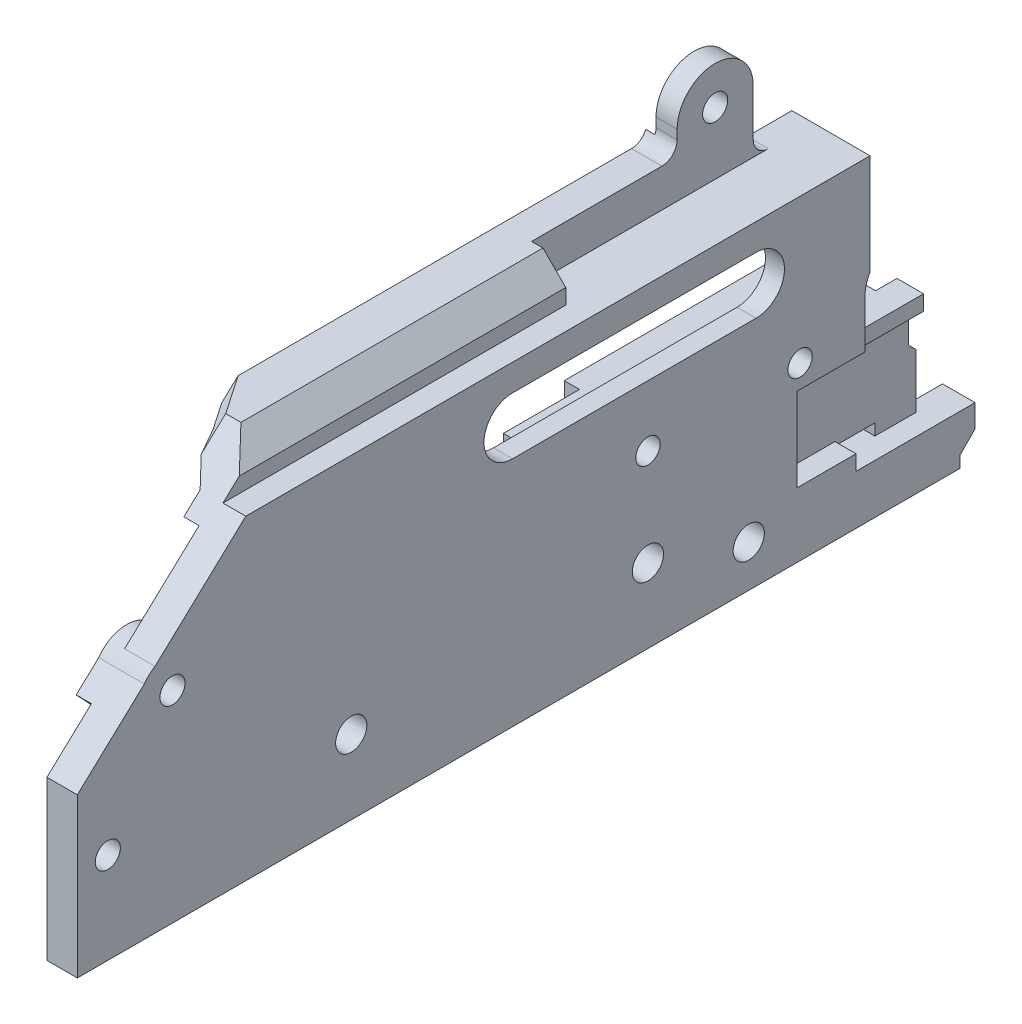
SolidWorks part; units mm, degrees
ref_plane "前视基准面" through (0, 0, 0) normal (0, 0, 1) x (1, 0, 0)
ref_plane "上视基准面" through (0, 0, 0) normal (0, 1, 0) x (1, 0, 0)
ref_plane "右视基准面" through (0, 0, 0) normal (1, 0, 0) x (0, 0, -1)
other "Configuration Table"
sketch "草图1" plane through (0, 0, 0) normal (1, 0, 0) x (0, 0, -1)
  line L0 (0, 0) -> (20, 0) construction
  line L2 (29.2, 6.5) -> (-4, 6.5)
  line L3 (29.2, 6.5) -> (29.2, -15.5)
  line L4 (29.2, -15.5) -> (-4, -15.5)
  line L5 (-4, 6.5) -> (-4, -15.5)
  circle A0 centre (0, 0) radius 1.6
  circle A1 centre (20, 0) radius 1.6
  dimension "D1" = 20
  dimension "D2" = 3.2
  dimension "D4" = 9.2
  dimension "D6" = 4
  dimension "D3" = 6.5
  dimension "D5" = 22
extrude "凸台-拉伸1" add sketch "草图1" along normal blind 7
sketch "草图2" plane through (7, 0, 0) normal (1, 0, 0) x (0, 0, -1)
  line L1 (-4, 6.5) -> (29.2, 6.5)
  line L2 (-4, 6.5) -> (-4, 17)
  line L3 (-4, 17) -> (29.2, 17)
  line L4 (29.2, 6.5) -> (29.2, 17)
  dimension "D1" = 10.5
extrude "凸台-拉伸2" add sketch "草图2" against normal offset from surface (2 mm away) 5 up to face at (0, 0, -1.6)
sketch "草图3" plane through (0, 0, 4) normal (0, 0, 1) x (1, 0, 0)
  line L1 (7, -15.5) -> (1, -15.5)
  line L2 (7, -15.5) -> (7, 6.5)
  line L3 (7, 6.5) -> (3, 6.5)
  line L4 (1, -15.5) -> (1, 4.5)
  line L5 (3, 6.5) -> (3, 4.5)
  line L6 (3, 4.5) -> (1, 4.5)
  line L7 (5, 6.5) -> (0, 6.5) construction
  dimension "D1" = 6
  dimension "D2" = 2
  dimension "D3" = 2
extrude "凸台-拉伸3" add sketch "草图3" along normal blind 60
sketch "草图4" plane through (0, 0, 4) normal (0, 0, 1) x (1, 0, 0)
  line L4 (5, 6.5) -> (7, 6.5)
  line L5 (7, 6.5) -> (7, 17)
  line L6 (7, 17) -> (5, 17)
  line L7 (5, 17) -> (5, 6.5)
  line L8 (5, 6.5) -> (7, 6.5)
  line L9 (7, 6.5) -> (7, 17)
  line L10 (7, 17) -> (5, 17)
  line L11 (5, 17) -> (5, 6.5)
  dimension "D1" = 0
extrude "凸台-拉伸4" add sketch "草图4" along normal blind 38.5
sketch "草图5" plane through (0, 0, 42.5) normal (0, 0, 1) x (1, 0, 0)
  line L0 (7, 6.5) -> (7, 17) construction
  line L1 (7, 6.5) -> (3, 6.5)
  line L2 (7, 6.5) -> (7, 17)
  line L3 (7, 17) -> (3, 17)
  line L4 (3, 6.5) -> (3, 17)
  line L5 (7, 17) -> (5, 17) construction
extrude "凸台-拉伸5" add sketch "草图5" along normal blind 2
sketch "草图6" plane through (0, 0, 44.5) normal (0, 0, 1) x (1, 0, 0)
  line L4 (7, 6.5) -> (7, 17)
  line L5 (7, 17) -> (3, 17)
  line L6 (3, 17) -> (3, 6.5)
  line L7 (3, 6.5) -> (7, 6.5)
  line L8 (7, 6.5) -> (7, 17)
  line L9 (7, 17) -> (3, 17)
  line L10 (3, 17) -> (3, 6.5)
  line L11 (3, 6.5) -> (7, 6.5)
  dimension "D1" = 0
extrude "凸台-拉伸6" add sketch "草图6" along normal up to surface (19.5 mm away) up to face at (3.6667, -1.5, 64)
sketch "草图7" plane through (0, 17, 0) normal (0, 1, 0) x (1, 0, 0)
  line L0 (1, -64) -> (1, -4) construction
  line L1 (7, 29.2) -> (1, 29.2)
  line L2 (7, 29.2) -> (7, -64)
  line L3 (7, -64) -> (1, -64)
  line L4 (1, 29.2) -> (1, -64)
  line L5 (7, -64) -> (3, -64) construction
extrude "凸台-拉伸7" add sketch "草图7" along normal blind 2
sketch "草图8" plane through (1, 0, 0) normal (-1, 0, 0) x (0, 0, 1)
  line L1 (-29.2, 19) -> (64, 19)
  line L2 (-29.2, 19) -> (-29.2, 24)
  line L3 (-29.2, 24) -> (64, 24)
  line L4 (64, 19) -> (64, 24)
  dimension "D1" = 5
extrude "凸台-拉伸8" add sketch "草图8" against normal blind 3
sketch "草图10" plane through (1, 0, 0) normal (-1, 0, 0) x (0, 0, 1)
  line L1 (-29.2, 24) -> (64, 24)
  line L2 (-29.2, 24) -> (-29.2, 22)
  line L3 (-29.2, 22) -> (64, 22)
  line L4 (64, 24) -> (64, 22)
  line L5 (64, 24) -> (64, 17) construction
  dimension "D1" = 2
extrude "凸台-拉伸9" add sketch "草图10" along normal blind 5.5
sketch "草图12" plane through (-4.5, 0, 0) normal (-1, 0, 0) x (0, 0, 1)
  line L0 (64, 24) -> (-29.2, 24) construction
  line L1 (-29.2, 22) -> (-11.2, 22)
  line L2 (-29.2, 22) -> (-29.2, 24)
  line L3 (-29.2, 24) -> (-11.2, 24)
  line L4 (-11.2, 22) -> (-11.2, 24)
  dimension "D1" = 18
extrude "切除-拉伸1" cut sketch "草图12" against normal up to surface (5.5 mm away) up to face at (1, 19.5, 17.4)
sketch "草图13" plane through (1, 0, 0) normal (-1, 0, 0) x (0, 0, 1)
  line L0 (-11.2, 22) -> (64, 22) construction
  line L1 (10.8, 22) -> (-29.2, 22)
  line L2 (10.8, 22) -> (10.8, 17)
  line L3 (10.8, 17) -> (-29.2, 17)
  line L4 (-29.2, 22) -> (-29.2, 17)
  dimension "D1" = 40
extrude "凸台-拉伸10" add sketch "草图13" along normal blind 3.5
sketch "草图14" plane through (-2.5, 0, 0) normal (-1, 0, 0) x (0, 0, 1)
  line L0 (-29.2, 17) -> (10.8, 17) construction
  line L1 (-11.2, 19.8) -> (-9.2, 19.8)
  line L2 (-11.2, 19.8) -> (-11.2, 17)
  line L3 (-11.2, 17) -> (-9.2, 17)
  line L4 (-9.2, 19.8) -> (-9.2, 17)
  line L5 (10.8, 22) -> (-11.2, 22) construction
  line L6 (-11.2, 22) -> (-11.2, 24) construction
  dimension "D1" = 2
  dimension "D2" = 2.2
sketch "草图15" plane through (4, 0, 0) normal (1, 0, 0) x (0, 0, -1)
  line L0 (29.2, 19) -> (-64, 19) construction
  line L1 (29.2, 24) -> (13.7, 24)
  line L2 (29.2, 24) -> (29.2, 19)
  line L3 (29.2, 19) -> (13.7, 19)
  line L4 (13.7, 24) -> (13.7, 19)
  line L6 (11.2, 22) -> (11.2, 24) construction
  dimension "D1" = 2.5
extrude "切除-拉伸2" cut sketch "草图15" against normal up to next
sketch "草图16" plane through (0, 22, 0) normal (0, 1, 0) x (1, 0, 0)
  line L4 (1, 11.2) -> (1, 13.7)
  line L5 (1, 13.7) -> (-2.5, 13.7)
  line L6 (-2.5, 13.7) -> (-2.5, 11.2)
  line L7 (-2.5, 11.2) -> (1, 11.2)
  line L8 (1, 11.2) -> (1, 13.7)
  line L9 (1, 13.7) -> (-2.5, 13.7)
  line L10 (-2.5, 13.7) -> (-2.5, 11.2)
  line L11 (-2.5, 11.2) -> (1, 11.2)
  dimension "D1" = 0
extrude "凸台-拉伸12" add sketch "草图16" along normal up to surface (2 mm away) up to face at (0.1667, 24, 13.0333)
sketch "草图17" plane through (7, 0, 0) normal (1, 0, 0) x (0, 0, -1)
  line L0 (-47.5, 24) -> (-64, 8.6135)
  line L1 (-64, 24) -> (13.7, 24) construction
  line L2 (-64, -15.5) -> (-64, 19) construction
  line L3 (-64, 8.6135) -> (-64, 24)
  line L4 (-64, 24) -> (-47.5, 24)
  dimension "D1" = 133
  dimension "D2" = 16.5
extrude "切除-拉伸3" cut sketch "草图17" against normal up to next
chamfer "倒角1" distance 3.5 angle 45 1 edges at (-4.5, 23, 48.5724)
sketch "草图18" plane through (-2.5, 0, 0) normal (-1, 0, 0) x (0, 0, 1)
  line L0 (-13.7, 19) -> (-13.7, 24) construction
  line L1 (-29.2, 19) -> (-13.7, 19) construction
  line L2 (-11.337, 27.2) -> (-11.337, 24)
  line L3 (-13.7, 24) -> (-11.2, 24) construction
  line L4 (-11.337, 24) -> (-13.7, 24)
  line L5 (-13.7, 24) -> (-13.7, 19)
  line L6 (-13.7, 19) -> (-21.337, 19)
  line L7 (-21.337, 19) -> (-21.337, 27.2)
  circle A0 centre (-16.337, 27.2) radius 1.65
  arc A1 (-11.337, 27.2) -> (-21.337, 27.2) centre (-16.337, 27.2) ccw
  dimension "D1" = 2.637
  dimension "D2" = 8.2
  dimension "D3" = 3.3
  dimension "D4" = 10
extrude "凸台-拉伸13" add sketch "草图18" against normal blind 2
fillet "圆角1" radius 2 2 edges at (-1.5, 24, -11.337) (-1.5, 19, -21.337)
sketch "草图19" plane through (0, 24, 0) normal (0, 1, 0) x (1, 0, 0)
  line L0 (-0.5, 9.337) -> (-0.5, 11.337) construction
  line L1 (4, 13.7) -> (-0.5, 13.7)
  line L2 (4, 13.7) -> (4, -7.8)
  line L3 (4, -7.8) -> (-0.5, -7.8)
  line L4 (-0.5, 13.7) -> (-0.5, -7.8)
  line L5 (-2.5, -10.8) -> (1, -10.8) construction
  dimension "D1" = 3
extrude "切除-拉伸4" cut sketch "草图19" against normal up to surface (5 mm away) up to face at (2, 19, -3.3438)
chamfer "倒角2" distance 3 angle 45 2 edges at (4, 24, 27.65) (1, 22, 30.2224)
sketch "草图20" plane through (7, 0, 0) normal (1, 0, 0) x (0, 0, -1)
  line L0 (-64, -15.5) -> (-64, 8.6135) construction
  line L1 (-64, -15.5) -> (29.2, -15.5) construction
  circle A0 centre (-62.5, 4) radius 1.65
  dimension "D1" = 1.5
  dimension "D2" = 19.5
  dimension "D3" = 3.3
extrude "切除-拉伸5" cut sketch "草图20" against normal up to next
sketch "草图21" plane through (1, 0, 0) normal (-1, 0, 0) x (0, 0, 1)
  circle A0 centre (62.5, 4) radius 1.65
  circle A1 centre (62.5, 4) radius 4.5
  dimension "D1" = 9
extrude "凸台-拉伸14" add sketch "草图21" against normal up to surface (6 mm away) up to face at (7, 3.3734, 35.3303)
sketch "草图22" plane through (1, 0, 0) normal (-1, 0, 0) x (0, 0, 1)
  line L3 (66.1986, 6.5633) -> (75, -1.6442)
  line L4 (75, -1.6442) -> (75, -15.5)
  line L5 (75, -15.5) -> (64, -15.5)
  line L6 (55.0066, 17) -> (64, 8.6135) construction
  line L7 (64, -0.2426) -> (64, -15.5)
  circle A2 centre (62.5, 4) radius 1.65 construction
  arc A3 (64, -0.2426) -> (58.0279, 4.5) centre (62.5, 4) ccw construction
  arc A4 (64, -0.2426) -> (66.1986, 6.5633) centre (62.5, 4) ccw
  dimension "D1" = 12.5
extrude "凸台-拉伸15" add sketch "草图22" against normal up to surface (6 mm away) up to face at (7, 3.3734, 36.2088)
sketch "草图23" plane through (7, 0, 0) normal (1, 0, 0) x (0, 0, -1)
  line L0 (-64, 8.6135) -> (-64.799, 7.8684)
  line L1 (-64.799, 7.8684) -> (-64, 8.2426)
  line L2 (-64, 8.2426) -> (-64, 8.6135)
  line L3 (-64, 8.6135) -> (-52.8618, 19) construction
  arc A0 (-64, 8.2426) -> (-66.1986, 6.5633) centre (-62.5, 4) ccw construction
extrude "凸台-拉伸16" add sketch "草图23" against normal up to surface (4 mm away) up to face at (3, 9.2872, 41.6414)
sketch "草图24" plane through (1, 0, 0) normal (-1, 0, 0) x (0, 0, 1)
  line L0 (75, -15.5) -> (75, -1.6442) construction
  line L1 (75, -15.5) -> (4, -15.5) construction
  circle A0 centre (71, -10.5) radius 1.65
  dimension "D1" = 3.3
  dimension "D2" = 4
  dimension "D3" = 5
extrude "切除-拉伸6" cut sketch "草图24" against normal up to next
sketch "草图25" plane through (5, 0, 0) normal (-1, 0, 0) x (0, 0, 1)
  line L0 (-29.2, 11.75) -> (42.5, 11.75) construction
  line L1 (-29.2, 6.5) -> (-29.2, 17) construction
  line L2 (42.5, 17) -> (42.5, 6.5) construction
  line L3 (17.8, 11.75) -> (-14.2, 11.75) construction
  line L4 (17.8, 8) -> (-14.2, 8)
  line L5 (17.8, 15.5) -> (-14.2, 15.5)
  arc A0 (17.8, 8) -> (17.8, 15.5) centre (17.8, 11.75) ccw
  arc A1 (-14.2, 15.5) -> (-14.2, 8) centre (-14.2, 11.75) ccw
  point P8 (1.8, 11.75)
  dimension "D1" = 47
  dimension "D2" = 15
  dimension "D3" = 7.5
extrude "切除-拉伸7" cut sketch "草图25" against normal up to next
sketch "草图26" plane through (0, 0, 42.5) normal (0, 0, -1) x (-1, 0, 0)
  line L4 (-5, 17) -> (-5, 6.5)
  line L5 (-5, 6.5) -> (-3, 6.5)
  line L6 (-3, 6.5) -> (-3, 17)
  line L7 (-3, 17) -> (-5, 17)
  line L8 (-5, 17) -> (-5, 6.5)
  line L9 (-5, 6.5) -> (-3, 6.5)
  line L10 (-3, 6.5) -> (-3, 17)
  line L11 (-3, 17) -> (-5, 17)
  dimension "D1" = 0
extrude "切除-拉伸8" cut sketch "草图26" against normal blind 5
sketch "草图27" plane through (0, 0, 4) normal (0, 0, 1) x (1, 0, 0)
  line L1 (1, 4.5) -> (3, 4.5)
  line L2 (1, 4.5) -> (1, 6.5)
  line L3 (1, 6.5) -> (3, 6.5)
  line L4 (3, 4.5) -> (3, 6.5)
extrude "凸台-拉伸17" add sketch "草图27" along normal blind 10
sketch "草图28" plane through (1, 0, 0) normal (-1, 0, 0) x (0, 0, 1)
  line L0 (67, 1.4943) -> (67, -15.5)
  line L2 (75, -15.5) -> (4, -15.5) construction
  line L3 (67, -15.5) -> (75, -15.5)
  line L4 (75, -15.5) -> (75, -1.6442)
  line L5 (75, -1.6442) -> (69.1556, 3.8058)
  line L6 (69.1556, 3.8058) -> (67, 1.4943)
  line L7 (75, -1.6442) -> (66.1986, 6.5633) construction
  circle A0 centre (62.5, 4) radius 1.65 construction
  dimension "D3" = 5
  dimension "D1" = 8
  dimension "D2" = 137
extrude "切除-拉伸9" cut sketch "草图28" against normal blind 2
sketch "草图29" plane through (7, 0, 0) normal (1, 0, 0) x (0, 0, -1)
  circle A0 centre (34, 3.1) radius 5.5
  circle A1 centre (20, 0) radius 1.6 construction
  dimension "D1" = 3.1
  dimension "D2" = 14
  dimension "D3" = 11
extrude "切除-拉伸10" cut sketch "草图29" against normal up to next
sketch "草图30" plane through (1, 0, 0) normal (-1, 0, 0) x (0, 0, 1)
  line L0 (4, 6.5) -> (4, -15.5) construction
  line L1 (4, -4.5) -> (67, -4.5)
  line L2 (4, -4.5) -> (4, -6.5)
  line L3 (4, -6.5) -> (67, -6.5)
  line L4 (67, -4.5) -> (67, -6.5)
  line L5 (67, 1.4943) -> (67, -15.5) construction
  circle A0 centre (0, 0) radius 1.6 construction
  dimension "D1" = 4.5
  dimension "D2" = 2
extrude "凸台-拉伸18" add sketch "草图30" along normal up to surface (1 mm away) up to face at (0, -1.9667, -18.0167)
sketch "草图31" plane through (5, 0, 0) normal (-1, 0, 0) x (0, 0, 1)
  line L0 (-14.2, 8) -> (17.8, 8) construction
  line L1 (17.8, 15.5) -> (-14.2, 15.5) construction
  line L2 (-14.2, 8) -> (17.8, 8)
  line L3 (17.8, 15.5) -> (-14.2, 15.5)
  line L4 (-29.2, 6.5) -> (47.5, 6.5)
  line L5 (47.5, 6.5) -> (47.5, 17)
  line L6 (47.5, 17) -> (-29.2, 17)
  line L7 (-29.2, 17) -> (-29.2, 6.5)
  line L8 (-29.2, 6.5) -> (47.5, 6.5)
  line L9 (47.5, 6.5) -> (47.5, 17)
  line L10 (47.5, 17) -> (-29.2, 17)
  line L11 (-29.2, 17) -> (-29.2, 6.5)
  arc A0 (17.8, 8) -> (17.8, 15.5) centre (17.8, 11.75) ccw construction
  arc A1 (-14.2, 15.5) -> (-14.2, 8) centre (-14.2, 11.75) ccw construction
  arc A2 (17.8, 8) -> (17.8, 15.5) centre (17.8, 11.75) ccw
  arc A3 (-14.2, 15.5) -> (-14.2, 8) centre (-14.2, 11.75) ccw
  dimension "D1" = 0
sketch "草图32" plane through (-2.5, 0, 0) normal (-1, 0, 0) x (0, 0, 1)
  line L8 (-11.2, 22) -> (-11.2, 25.2725)
  line L9 (-11.337, 26) -> (-11.337, 27.2)
  line L10 (-21.337, 27.2) -> (-21.337, 21)
  line L11 (-23.337, 19) -> (-29.2, 19)
  line L12 (-29.2, 19) -> (-29.2, 17)
  line L13 (-29.2, 17) -> (10.8, 17)
  line L14 (10.8, 17) -> (10.8, 22)
  line L15 (10.8, 22) -> (-11.2, 22)
  line L16 (-11.2, 22) -> (-11.2, 25.2725)
  line L17 (-11.337, 26) -> (-11.337, 27.2)
  line L18 (-21.337, 27.2) -> (-21.337, 21)
  line L19 (-23.337, 19) -> (-29.2, 19)
  line L20 (-29.2, 19) -> (-29.2, 17)
  line L21 (-29.2, 17) -> (10.8, 17)
  line L22 (10.8, 17) -> (10.8, 22)
  line L23 (10.8, 22) -> (-11.2, 22)
  circle A0 centre (-16.337, 27.2) radius 1.65 construction
  circle A1 centre (-16.337, 27.2) radius 1.65
  arc A3 (-11.337, 26) -> (-11.2, 25.2725) centre (-9.337, 26) ccw
  arc A4 (-11.337, 27.2) -> (-21.337, 27.2) centre (-16.337, 27.2) ccw
  arc A5 (-23.337, 19) -> (-21.337, 21) centre (-23.337, 21) ccw
  arc A6 (-11.337, 26) -> (-11.2, 25.2725) centre (-9.337, 26) ccw
  arc A7 (-11.337, 27.2) -> (-21.337, 27.2) centre (-16.337, 27.2) ccw
  arc A8 (-23.337, 19) -> (-21.337, 21) centre (-23.337, 21) ccw
  dimension "D1" = 0
extrude "凸台-拉伸19" add sketch "草图32" along normal blind 0.775
sketch "草图34" plane through (0, -15.5, 0) normal (0, -1, 0) x (1, 0, 0)
  line L8 (3, 75) -> (3, 67)
  line L9 (3, 67) -> (1, 67)
  line L10 (1, 67) -> (1, 4)
  line L11 (1, 4) -> (0, 4)
  line L12 (0, 4) -> (0, -29.2)
  line L13 (0, -29.2) -> (7, -29.2)
  line L14 (7, -29.2) -> (7, 75)
  line L15 (7, 75) -> (3, 75)
  line L16 (3, 75) -> (3, 67)
  line L17 (3, 67) -> (1, 67)
  line L18 (1, 67) -> (1, 4)
  line L19 (1, 4) -> (0, 4)
  line L20 (0, 4) -> (0, -29.2)
  line L21 (0, -29.2) -> (7, -29.2)
  line L22 (7, -29.2) -> (7, 75)
  line L23 (7, 75) -> (3, 75)
  dimension "D1" = 0
extrude "凸台-拉伸20" add sketch "草图34" along normal blind 5.5
sketch "草图35" plane through (0, 0, 0) normal (-1, 0, 0) x (0, 0, 1)
  line L1 (-24.2, -11) -> (-29.2, -11)
  line L2 (-24.2, -11) -> (-24.2, -21)
  line L3 (-24.2, -21) -> (-29.2, -21)
  line L4 (-29.2, -11) -> (-29.2, -21)
  dimension "D1" = 5
  dimension "D2" = 10
extrude "切除-拉伸12" cut sketch "草图35" against normal blind 1.225
sketch "草图36" plane through (0, 0, -29.2) normal (0, 0, -1) x (-1, 0, 0)
  line L1 (-1.225, -21) -> (-5.225, -21)
  line L2 (-1.225, -21) -> (-1.225, -11)
  line L3 (-1.225, -11) -> (-5.225, -11)
  line L4 (-5.225, -21) -> (-5.225, -11)
  dimension "D1" = 10
  dimension "D2" = 4
extrude "凸台-拉伸21" add sketch "草图36" along normal blind 5
sketch "草图37" plane through (5.225, 0, 0) normal (1, 0, 0) x (0, 0, -1)
  line L0 (34.2, -11) -> (34.2, -21) construction
  line L1 (33.6, -16) -> (28.85, -16)
  line L2 (33.6, -16) -> (33.6, -13)
  line L3 (33.6, -13) -> (28.85, -13)
  line L4 (28.85, -16) -> (28.85, -13)
  line L5 (34.2, -21) -> (29.2, -21) construction
  dimension "D1" = 5
  dimension "D2" = 3
  dimension "D3" = 5.35
  dimension "D4" = 0.6
extrude "切除-拉伸13" cut sketch "草图37" against normal up to next and the other way up to next
sketch "草图38" plane through (5.225, 0, 0) normal (1, 0, 0) x (0, 0, -1)
  line L0 (34.2, -11) -> (34.2, -21) construction
  line L1 (34.2, -14) -> (19.6, -14)
  line L2 (34.2, -14) -> (34.2, -3)
  line L3 (34.2, -3) -> (19.6, -3)
  line L4 (19.6, -14) -> (19.6, -3)
  line L5 (33.6, -16) -> (29.2, -16) construction
  line L7 (28.85, -16) -> (28.85, -13) construction
  dimension "D1" = 2
  dimension "D2" = 9.25
  dimension "D3" = 11
extrude "切除-拉伸14" cut sketch "草图38" along normal up to next and the other way blind 1
sketch "草图39" plane through (0, 0, -34.2) normal (0, 0, -1) x (-1, 0, 0)
  line L1 (-2.725, -1) -> (-4.225, -1)
  line L2 (-2.725, -1) -> (-2.725, -21)
  line L3 (-2.725, -21) -> (-4.225, -21)
  line L4 (-4.225, -1) -> (-4.225, -21)
  line L5 (-5.225, -21) -> (-1.225, -21) construction
  line L6 (-5.225, -14) -> (-5.225, -21) construction
  line L7 (-1.225, -11) -> (0, -11) construction
  dimension "D1" = 2.5
  dimension "D2" = 1
  dimension "D3" = 10
extrude "凸台-拉伸22" add sketch "草图39" along normal blind 5.8 and the other way up to next
sketch "草图40" plane through (0, 0, -29.2) normal (0, 0, -1) x (-1, 0, 0)
  line L1 (-1.225, -11) -> (-2.725, -11)
  line L2 (-1.225, -11) -> (-1.225, -1)
  line L3 (-1.225, -1) -> (-2.725, -1)
  line L4 (-2.725, -11) -> (-2.725, -1)
extrude "凸台-拉伸23" add sketch "草图40" along normal up to surface (5 mm away) up to face at (1.975, -16, -34.2)
sketch "草图41" plane through (4.225, 0, 0) normal (1, 0, 0) x (0, 0, -1)
  line L1 (40, -1) -> (39, -1)
  line L2 (40, -1) -> (40, -8)
  line L3 (40, -8) -> (39, -8)
  line L4 (39, -1) -> (39, -8)
  dimension "D1" = 1
  dimension "D2" = 7
extrude "切除-拉伸15" cut sketch "草图41" against normal up to next
chamfer "倒角3" distance 1 angle 45 1 edges at (3.475, -8, -39)
sketch "草图42" plane through (0, 0, -29.2) normal (0, 0, -1) x (-1, 0, 0)
  line L1 (-4.225, -21) -> (-7, -21)
  line L2 (-4.225, -21) -> (-4.225, -16)
  line L3 (-4.225, -16) -> (-7, -16)
  line L4 (-7, -21) -> (-7, -16)
extrude "凸台-拉伸24" add sketch "草图42" along normal up to surface (10.8 mm away) up to face at (3.475, -14.5, -40)
sketch "草图43" plane through (4.225, 0, 0) normal (1, 0, 0) x (0, 0, -1)
  line L4 (33.6, -16) -> (34.2, -16)
  line L5 (34.2, -16) -> (34.2, -14)
  line L6 (34.2, -14) -> (33.6, -14)
  line L7 (33.6, -14) -> (33.6, -16)
  line L8 (33.6, -16) -> (34.2, -16)
  line L9 (34.2, -16) -> (34.2, -14)
  line L10 (34.2, -14) -> (33.6, -14)
  line L11 (33.6, -14) -> (33.6, -16)
  dimension "D1" = 0
extrude "切除-拉伸16" cut sketch "草图43" along normal up to next
sketch "草图44" plane through (4.225, 0, 0) normal (1, 0, 0) x (0, 0, -1)
  line L1 (29.2, -3) -> (39, -3)
  line L2 (29.2, -3) -> (29.2, -1)
  line L3 (29.2, -1) -> (39, -1)
  line L4 (39, -3) -> (39, -1)
extrude "凸台-拉伸25" add sketch "草图44" along normal offset from surface (2 mm away) 0.775 up to face at (7, 0, -21.6)
sketch "草图45" plane through (7, 0, 0) normal (1, 0, 0) x (0, 0, -1)
  line L0 (39, -3) -> (19.6, -3) construction
  line L1 (28.5, 3.1) -> (29.3, 3.1)
  line L2 (28.5, 3.1) -> (28.5, -3)
  line L3 (28.5, -3) -> (29.3, -3)
  line L4 (29.3, 3.1) -> (29.3, -3)
  arc A0 (29.2, 5.7851) -> (29.2, 0.4149) centre (34, 3.1) ccw construction
extrude "切除-拉伸17" cut sketch "草图45" against normal up to surface (0.775 mm away) up to face at (6.225, -2, -34.1)
sketch "草图46" plane through (7, 0, 0) normal (1, 0, 0) x (0, 0, -1)
  circle A0 centre (13.25, -17) radius 2.05
  circle A1 centre (20, 0) radius 1.6 construction
  dimension "D1" = 17
  dimension "D2" = 6.75
  dimension "D3" = 4.1
extrude "切除-拉伸18" cut sketch "草图46" against normal up to next
sketch "草图47" plane through (1, 0, 0) normal (-1, 0, 0) x (0, 0, 1)
  line L0 (62.5, -0.5) -> (67, -0.5)
  line L8 (4, -4.5) -> (67, -4.5)
  line L9 (67, -4.5) -> (67, 1.4943)
  line L10 (67, 1.4943) -> (69.1556, 3.8058)
  line L11 (69.1556, 3.8058) -> (66.1986, 6.5633)
  line L12 (58.0279, 4.5) -> (14, 4.5)
  line L13 (14, 4.5) -> (14, 6.5)
  line L14 (14, 6.5) -> (4, 6.5)
  line L15 (4, 6.5) -> (4, -4.5)
  line L16 (4, -4.5) -> (67, -4.5)
  line L17 (67, -4.5) -> (67, -0.5)
  line L20 (58.0279, 4.5) -> (14, 4.5)
  line L21 (14, 4.5) -> (14, 6.5)
  line L22 (14, 6.5) -> (4, 6.5)
  line L23 (4, 6.5) -> (4, -4.5)
  arc A0 (58.0279, 4.5) -> (62.5, -0.5) centre (62.5, 4) ccw
  arc A1 (66.1986, 6.5633) -> (58.0279, 4.5) centre (62.5, 4) ccw
  dimension "D1" = 0
extrude "切除-拉伸19" cut sketch "草图47" against normal blind 1
sketch "草图48" plane through (0, -21, 0) normal (0, -1, 0) x (1, 0, 0)
  line L0 (0, 58) -> (7, 58) construction
  line L1 (3.5, 58) -> (3.5, -18) construction
  line L2 (7, -40) -> (7, 75) construction
  line L3 (7, 75) -> (3, 75) construction
  line L4 (0, 4) -> (0, 67) construction
  circle A0 centre (3.5, 58) radius 2.05
  circle A1 centre (3.5, 20) radius 2.05
  circle A2 centre (3.5, -18) radius 2.05
  dimension "D1" = 4.1
  dimension "D3" = 38
  dimension "D4" = 38
  dimension "D2" = 17
extrude "切除-拉伸20" cut sketch "草图48" against normal blind 5
sketch "草图50" plane through (0, 0, 67) normal (0, 0, 1) x (1, 0, 0)
  line L0 (0, -21) -> (0, -3.5)
  line L2 (0, -3.5) -> (0.5, -3.5)
  line L3 (0.5, -3.5) -> (0.5, -21)
  line L5 (0.5, -21) -> (0, -21)
  line L7 (0, 6.5) -> (0, -4.5) construction
  line L8 (0, -4.5) -> (2, -4.5) construction
  dimension "D1" = 0.5
  dimension "D2" = 1
extrude "切除-拉伸21" cut sketch "草图50" against normal up to next
sketch "草图51" plane through (0, 0, -28.85) normal (0, 0, -1) x (-1, 0, 0)
  line L6 (-4.225, -14) -> (-7, -14)
  line L7 (-7, -14) -> (-7, -16)
  line L8 (-7, -16) -> (-1.225, -16)
  line L9 (-1.225, -16) -> (-1.225, -13)
  line L10 (-1.225, -13) -> (-4.225, -13)
  line L11 (-4.225, -13) -> (-4.225, -14)
  line L12 (-4.225, -14) -> (-7, -14)
  line L13 (-7, -14) -> (-7, -16)
  line L14 (-7, -16) -> (-1.225, -16)
  line L15 (-1.225, -16) -> (-1.225, -13)
  line L16 (-1.225, -13) -> (-4.225, -13)
  line L17 (-4.225, -13) -> (-4.225, -14)
  dimension "D1" = 0
extrude "切除-拉伸22" cut sketch "草图51" against normal blind 3
sketch "草图52" plane through (0, -21, 0) normal (0, -1, 0) x (1, 0, 0)
  line L0 (1, 59.6583) -> (1, 56.3417)
  line L1 (1, 67) -> (1, 4) construction
  line L2 (1, 21.6583) -> (1, 18.3417)
  arc A0 (1, 59.6583) -> (1, 56.3417) centre (3.5, 58) ccw
  arc A1 (1, 21.6583) -> (1, 18.3417) centre (3.5, 20) ccw
  circle A3 centre (3.5, 20) radius 2.05 construction
  dimension "D1" = 6
extrude "凸台-拉伸26" add sketch "草图52" against normal up to surface (14.5 mm away) up to face at (0.75, -6.5, 35.5)
sketch "草图53" plane through (1, 0, 0) normal (-1, 0, 0) x (0, 0, 1)
  line L0 (67, 1.4943) -> (67, -21) construction
  line L2 (4, -21) -> (4, -19)
  line L3 (4, -19) -> (18.3417, -19)
  line L4 (67, -21) -> (67, -19)
  line L5 (21.6583, -19) -> (56.3417, -19)
  line L6 (56.3417, -6.5) -> (59.6583, -6.5)
  line L7 (56.3417, -6.5) -> (56.3417, -19)
  line L9 (59.6583, -6.5) -> (59.6583, -19)
  line L10 (18.3417, -6.5) -> (21.6583, -6.5)
  line L11 (18.3417, -6.5) -> (18.3417, -19)
  line L13 (21.6583, -6.5) -> (21.6583, -19)
  line L14 (59.6583, -19) -> (66, -19)
  line L15 (59.6583, -6.5) -> (59.6583, -21) construction
  line L16 (21.6583, -6.5) -> (21.6583, -21) construction
  line L17 (4, -21) -> (67, -21)
  line L18 (67, -6.5) -> (67, -4.5) construction
  line L19 (67, -6.5) -> (66, -6.5)
  line L20 (67, -6.5) -> (67, -19)
  line L22 (66, -6.5) -> (66, -19)
  line L23 (59.6583, -6.5) -> (67, -6.5) construction
  dimension "D1" = 2
  dimension "D2" = 1
extrude "凸台-拉伸27" add sketch "草图53" along normal up to surface (0.5 mm away) up to face at (0.5, -8.8333, 10.1)
sketch "草图54" plane through (1, 0, 0) normal (-1, 0, 0) x (0, 0, 1)
  line L0 (21.6583, -6.5) -> (56.3417, -6.5) construction
  line L1 (24.6583, -6.5) -> (53.3417, -6.5)
  line L2 (24.6583, -6.5) -> (24.6583, -19)
  line L3 (24.6583, -19) -> (53.3417, -19)
  line L4 (53.3417, -6.5) -> (53.3417, -19)
  line L5 (21.6583, -19) -> (56.3417, -19) construction
  line L6 (18.3417, -6.5) -> (18.3417, -19) construction
  line L7 (4, -6.5) -> (15.3417, -6.5)
  line L8 (4, -6.5) -> (4, -19)
  line L9 (4, -19) -> (15.3417, -19)
  line L10 (15.3417, -6.5) -> (15.3417, -19)
  line L11 (4, -19) -> (18.3417, -19) construction
  line L12 (21.6583, -6.5) -> (21.6583, -19) construction
  line L13 (56.3417, -6.5) -> (56.3417, -19) construction
  dimension "D1" = 3
  dimension "D2" = 3
  dimension "D3" = 3
extrude "切除-拉伸23" cut sketch "草图54" against normal blind 3
sketch "草图55" plane through (0.5, 0, 0) normal (-1, 0, 0) x (0, 0, 1)
  line L0 (4, -18.3367) -> (17.5807, -6.5)
  line L1 (4, -19) -> (4, -6.5) construction
  line L2 (15.3417, -6.5) -> (18.3417, -6.5) construction
  line L3 (4, -19) -> (18.3417, -6.5) construction
  line L4 (21.6583, -6.5) -> (56.3417, -19) construction
  line L5 (66, -19) -> (59.6583, -6.5) construction
  line L6 (56.3417, -6.5) -> (21.6583, -19) construction
  line L7 (18.3417, -7.1633) -> (4.761, -19)
  line L8 (18.3417, -19) -> (18.3417, -6.5) construction
  line L9 (4, -19) -> (15.3417, -19) construction
  line L10 (17.5807, -6.5) -> (18.3417, -6.5)
  line L11 (18.3417, -6.5) -> (18.3417, -7.1633)
  line L12 (4, -18.3367) -> (4, -19)
  line L13 (4, -19) -> (4.761, -19)
  line L14 (23.133, -6.5) -> (39, -12.2185)
  line L15 (21.6583, -6.5) -> (24.6583, -6.5) construction
  line L16 (56.3417, -19) -> (56.3417, -6.5) construction
  line L17 (54.867, -19) -> (39, -13.2815)
  line L18 (21.6583, -19) -> (56.3417, -19) construction
  line L19 (21.6583, -6.5) -> (21.6583, -19) construction
  line L20 (21.6583, -18.4685) -> (37.5253, -12.75)
  line L21 (21.6583, -6.5) -> (56.3417, -6.5) construction
  line L22 (23.133, -19) -> (39, -13.2815)
  line L23 (39, -12.2185) -> (54.867, -6.5)
  line L24 (40.4747, -12.75) -> (56.3417, -18.4685)
  line L25 (37.5253, -12.75) -> (21.6583, -7.0315)
  line L26 (40.4747, -12.75) -> (56.3417, -7.0315)
  line L27 (23.133, -6.5) -> (21.6583, -6.5)
  line L28 (21.6583, -6.5) -> (21.6583, -7.0315)
  line L29 (54.867, -6.5) -> (56.3417, -6.5)
  line L30 (56.3417, -6.5) -> (56.3417, -7.0315)
  line L31 (56.3417, -18.4685) -> (56.3417, -19)
  line L32 (56.3417, -19) -> (54.867, -19)
  line L33 (23.133, -19) -> (21.6583, -19)
  line L34 (21.6583, -19) -> (21.6583, -18.4685)
  line L35 (59.6583, -7.6051) -> (65.4393, -19)
  line L36 (59.6583, -6.5) -> (59.6583, -19) construction
  line L37 (59.6583, -19) -> (66, -19) construction
  line L38 (60.219, -6.5) -> (66, -17.8949)
  line L39 (59.6583, -6.5) -> (66, -6.5) construction
  line L40 (66, -6.5) -> (66, -19) construction
  line L41 (59.6583, -7.6051) -> (59.6583, -6.5)
  line L42 (59.6583, -6.5) -> (60.219, -6.5)
  line L43 (66, -17.8949) -> (66, -19)
  line L44 (66, -19) -> (65.4393, -19)
  dimension "D1" = 1
  dimension "D2" = 1
  dimension "D3" = 1
  dimension "D4" = 1
extrude "凸台-拉伸28" add sketch "草图55" against normal up to next
fillet "圆角2" radius 0.8 30 edges at (0.75, -19, 18.3417) (2.5, -19, 15.3417) (2.5, -6.5, 15.3417) (2.25, -6.5, 4) (0.75, -7.1633, 18.3417) (0.75, -6.5, 17.5807) (2.5, -9.778, 15.3417) (2.5, -8.4515, 15.3417) (2.25, -18.3367, 4) (2.25, -19, 4.761) (2.25, -12.75, 37.5253) (2.25, -13.2815, 39) (2.25, -12.2185, 39) (2.25, -12.75, 40.4747) (2.5, -8.1127, 53.3417) (2.5, -17.3873, 53.3417) (0.75, -18.4685, 56.3417) (0.75, -7.0315, 56.3417) (0.75, -6.5, 54.867) (0.75, -19, 54.867) (0.75, -19, 23.133) (0.75, -6.5, 23.133) (0.75, -18.4685, 21.6583) (0.75, -7.0315, 21.6583) (0.75, -17.8949, 66) (0.75, -19, 59.6583) (0.75, -19, 65.4393) (0.75, -6.5, 66) (0.75, -6.5, 60.219) (0.75, -7.6051, 59.6583)
sketch "草图56" plane through (0.5, 0, 0) normal (-1, 0, 0) x (0, 0, 1)
  line L0 (35.9658, -12.75) -> (42.0342, -12.75) construction
  line L1 (39, -12.1681) -> (39, -13.3319) construction
  arc A0 (35.4371, -13.5026) -> (35.4371, -11.9974) centre (35.1658, -12.75) ccw construction
  arc A1 (42.5629, -11.9974) -> (42.5629, -13.5026) centre (42.8342, -12.75) ccw construction
  arc A2 (38.7288, -12.1208) -> (39.2712, -12.1208) centre (39, -11.3681) ccw construction
  arc A3 (39.2712, -13.3792) -> (38.7288, -13.3792) centre (39, -14.1319) ccw construction
  circle A4 centre (39, -12.75) radius 2.05
  circle A5 centre (39, -12.75) radius 4
  dimension "D1" = 4.1
  dimension "D2" = 8
extrude "凸台-拉伸29" add sketch "草图56" against normal up to next (3.5 mm away)
fillet "圆角3" radius 0.8 8 edges at (2.25, -14.566, 35.436) (2.25, -14.566, 42.564) (2.25, -13.6252, 42.9031) (2.25, -11.8748, 42.9031) (2.25, -10.934, 42.564) (2.25, -10.934, 35.436) (2.25, -13.6252, 35.0969) (2.25, -11.8748, 35.0969)
sketch "草图57" plane through (0.5, 0, 0) normal (-1, 0, 0) x (0, 0, 1)
  line L0 (0, 0) -> (0, -12.75) construction
  line L1 (0, -12.75) -> (39, -12.75) construction
  circle A0 centre (39, -12.75) radius 2.05
  circle A1 centre (0, -12.75) radius 2.05
extrude "切除-拉伸24" cut sketch "草图57" against normal up to next
sketch "草图58" plane through (0.5, 0, 0) normal (-1, 0, 0) x (0, 0, 1)
  line L0 (-29.2, -3.5) -> (4, -3.5) construction
  line L1 (-19.2, -4.5) -> (-4, -4.5)
  line L2 (-19.2, -4.5) -> (-19.2, -13)
  line L3 (-19.2, -13) -> (-4, -13)
  line L4 (-4, -4.5) -> (-4, -13)
  line L5 (-24.2, -11) -> (-24.2, -21) construction
  circle A0 centre (-13.25, -17) radius 2.05 construction
  circle A1 centre (0, -12.75) radius 2.05 construction
  dimension "D1" = 4
  dimension "D2" = 4
  dimension "D3" = 1
  dimension "D4" = 5
extrude "切除-拉伸25" cut sketch "草图58" against normal up to surface (3.5 mm away) up to face at (4, -9.7828, 9.7862)
fillet "圆角4" radius 0.8 4 edges at (2.25, -13, -4) (2.25, -13, -19.2) (2.25, -4.5, -19.2) (2.25, -4.5, -4)
extrude "凸台-拉伸30" add sketch "草图31" along normal blind 0.5
sketch "草图59" plane through (2.725, 0, 0) normal (-1, 0, 0) x (0, 0, 1)
  line L0 (-25.85, -13) -> (-33.6, -13) construction
  line L1 (-34.2, -21) -> (-31.6, -21)
  line L2 (-34.2, -21) -> (-34.2, -11)
  line L3 (-34.2, -11) -> (-31.6, -11)
  line L4 (-31.6, -21) -> (-31.6, -11)
  line L5 (-33.6, -13) -> (-33.6, -16) construction
  dimension "D1" = 2
  dimension "D2" = 2
extrude "切除-拉伸26" cut sketch "草图59" along normal up to next
sketch "草图60" plane through (2.725, 0, 0) normal (-1, 0, 0) x (0, 0, 1)
  line L0 (-37, -1) -> (-37, -7.8284)
  line L1 (-34.2, -1) -> (-39, -1) construction
  line L2 (-37, -7.8284) -> (-38, -8.8284)
  line L4 (-38, -8.8284) -> (-38, -21)
  line L5 (-40, -21) -> (-31.6, -21) construction
  line L6 (-38, -21) -> (-40, -21)
  line L7 (-40, -21) -> (-40, -8)
  line L8 (-40, -8) -> (-39, -7)
  line L9 (-39, -7) -> (-39, -1)
  line L10 (-39, -1) -> (-37, -1)
  dimension "D1" = 2
  dimension "D2" = 2
  dimension "D3" = 2
extrude "切除-拉伸27" cut sketch "草图60" against normal up to next
sketch "草图61" plane through (4.225, 0, 0) normal (1, 0, 0) x (0, 0, -1)
  line L0 (32.6, -16) -> (32.6, -14.5)
  line L1 (38, -16) -> (25.85, -16) construction
  line L2 (32.6, -14.5) -> (27.35, -14.5)
  line L3 (27.35, -14.5) -> (27.35, -16)
  line L4 (27.35, -16) -> (25.85, -16)
  line L5 (25.85, -16) -> (25.85, -13)
  line L6 (25.85, -13) -> (33.6, -13)
  line L7 (33.6, -13) -> (33.6, -16)
  line L8 (33.6, -16) -> (32.6, -16)
  dimension "D1" = 1.5
  dimension "D2" = 1
  dimension "D3" = 1.5
extrude "凸台-拉伸31" add sketch "草图61" against normal up to surface (1.5 mm away) up to face at (2.725, -11.7214, -34.3333)
sketch "草图62" plane through (0, 0, -25.85) normal (0, 0, -1) x (-1, 0, 0)
  line L4 (-4.225, -16) -> (-4.225, -14)
  line L5 (-4.225, -14) -> (-7, -14)
  line L6 (-7, -14) -> (-7, -16)
  line L7 (-7, -16) -> (-4.225, -16)
  line L8 (-4.225, -16) -> (-4.225, -14)
  line L9 (-4.225, -14) -> (-7, -14)
  line L10 (-7, -14) -> (-7, -16)
  line L11 (-7, -16) -> (-4.225, -16)
  dimension "D1" = 0
extrude "凸台-拉伸32" add sketch "草图62" along normal up to surface (1.5 mm away) up to face at (3.475, -15.25, -27.35)
sketch "草图63" plane through (2.725, 0, 0) normal (-1, 0, 0) x (0, 0, 1)
  line L0 (-31.6, -13) -> (-31.6, -14.5)
  line L1 (-27.35, -14.5) -> (-32.6, -14.5) construction
  line L2 (-31.6, -14.5) -> (-27.35, -14.5)
  line L3 (-27.35, -14.5) -> (-27.35, -16)
  line L4 (-27.35, -16) -> (-25.85, -16)
  line L5 (-25.85, -16) -> (-25.85, -13)
  line L6 (-25.85, -13) -> (-31.6, -13)
extrude "凸台-拉伸33" add sketch "草图63" along normal up to surface (1.5 mm away) up to face at (1.225, -12.1667, -29.4417)
sketch "草图64" plane through (0, 0, -38) normal (0, 0, -1) x (-1, 0, 0)
  line L1 (-7, -16) -> (-2.725, -16)
  line L2 (-7, -16) -> (-7, -21)
  line L3 (-7, -21) -> (-2.725, -21)
  line L4 (-2.725, -16) -> (-2.725, -21)
extrude "凸台-拉伸34" add sketch "草图64" along normal blind 5
chamfer "倒角4" distance 2 angle 45 1 edges at (4.8625, -21, -43)
sketch "草图65" plane through (0, -21, 0) normal (0, -1, 0) x (1, 0, 0)
  line L10 (2.725, -31.6) -> (2.725, -41)
  line L11 (2.725, -41) -> (7, -41)
  line L12 (7, -41) -> (7, 75)
  line L13 (7, 75) -> (3, 75)
  line L14 (3, 75) -> (3, 67)
  line L15 (3, 67) -> (0.5, 67)
  line L16 (0.5, 67) -> (0.5, -24.2)
  line L17 (0.5, -24.2) -> (1.225, -24.2)
  line L18 (1.225, -24.2) -> (1.225, -31.6)
  line L19 (1.225, -31.6) -> (2.725, -31.6)
  line L20 (2.725, -31.6) -> (2.725, -41)
  line L21 (2.725, -41) -> (7, -41)
  line L22 (7, -41) -> (7, 75)
  line L23 (7, 75) -> (3, 75)
  line L24 (3, 75) -> (3, 67)
  line L25 (3, 67) -> (0.5, 67)
  line L26 (0.5, 67) -> (0.5, -24.2)
  line L27 (0.5, -24.2) -> (1.225, -24.2)
  line L28 (1.225, -24.2) -> (1.225, -31.6)
  line L29 (1.225, -31.6) -> (2.725, -31.6)
  circle A0 centre (3.5, -18) radius 2.05 construction
  circle A1 centre (3.5, 20) radius 2.05 construction
  circle A2 centre (3.5, 58) radius 2.05 construction
  circle A3 centre (3.5, -18) radius 2.05
  circle A4 centre (3.5, 20) radius 2.05
  circle A5 centre (3.5, 58) radius 2.05
  dimension "D1" = 0
extrude "凸台-拉伸35" add sketch "草图65" along normal blind 1.5
